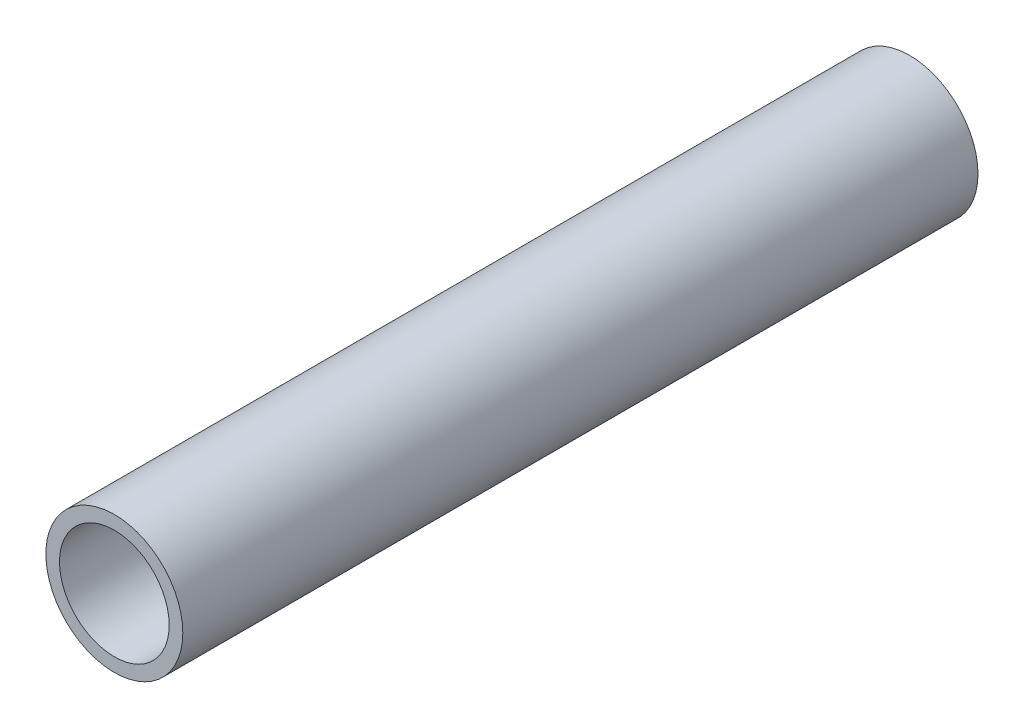
SolidWorks part; units mm, degrees
material "Plain Carbon Steel"
ref_plane "Front Plane" through (0, 0, 0) normal (0, 0, 1) x (1, 0, 0)
ref_plane "Top Plane" through (0, 0, 0) normal (0, 1, 0) x (1, 0, 0)
ref_plane "Right Plane" through (0, 0, 0) normal (1, 0, 0) x (0, 0, -1)
sketch "Sketch1" plane through (0, 0, 0) normal (0, 0, 1) x (1, 0, 0)
  circle A0 centre (0, 0) radius 15.9385
  circle A1 centre (0, 0) radius 12.7635
  dimension "D1" = 31.877
  dimension "D2" = 3.175
extrude "Boss-Extrude1" add sketch "Sketch1" along normal blind 185.1025
ref_axis "Axis1" through (0, 0, 185.1025) along (0, 0, -1)
sketch "Sketch2" plane through (0, 0, 185.1025) normal (0, 0, 1) x (1, 0, 0)
  line L0 (-15.9385, 0) -> (15.9385, 0) construction
  circle A0 centre (0, 0) radius 15.9385 construction
